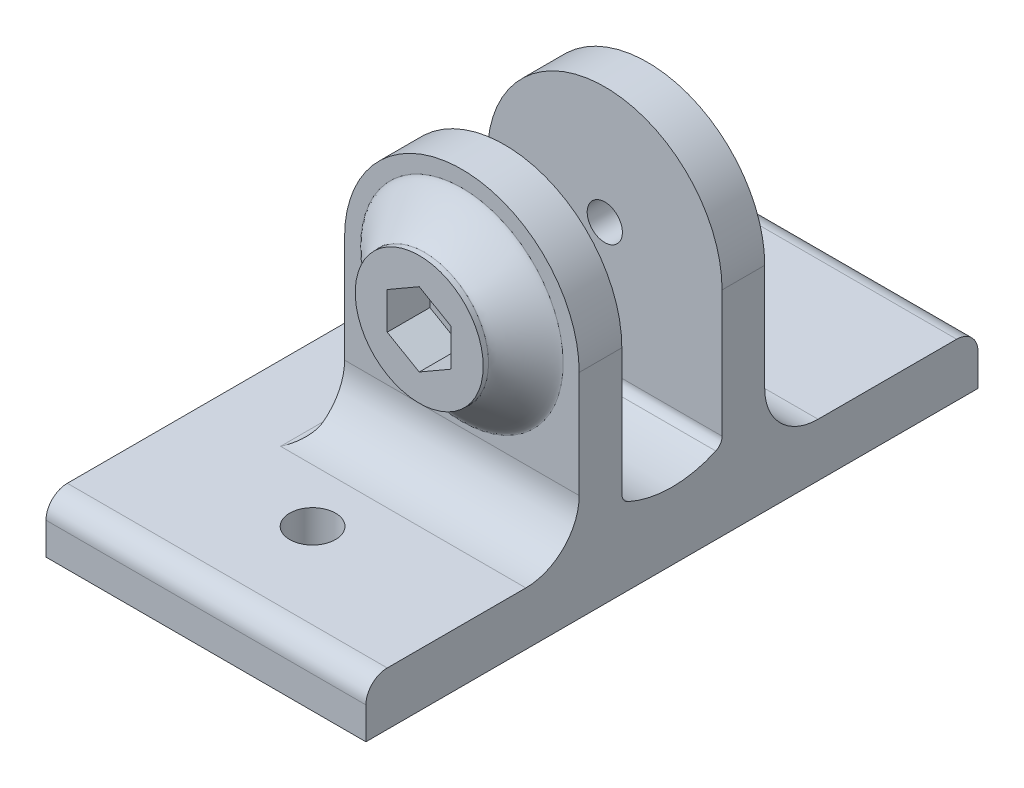
SolidWorks part; units mm, degrees
ref_plane "Front Plane" through (0, 0, 0) normal (0, 0, 1) x (1, 0, 0)
ref_plane "Top Plane" through (0, 0, 0) normal (0, 1, 0) x (1, 0, 0)
ref_plane "Right Plane" through (0, 0, 0) normal (1, 0, 0) x (0, 0, -1)
sketch "Croquis1" plane through (0, 0, 0) normal (0, 0, 1) x (1, 0, 0)
  line L0 (25.3159, 0) -> (-25.3159, 0) construction
  line L1 (11, 0) -> (11, -20)
  line L2 (11, -20) -> (-19, -20)
  line L3 (-11, 0) -> (-11, -15)
  line L6 (-11, -15) -> (-19, -15)
  line L7 (-19, -15) -> (-19, -20)
  arc A0 (11, 0) -> (-11, 0) centre (0, 0) ccw
  circle A1 centre (0, 0) radius 9 construction
  circle A5 centre (0, 0) radius 1.65
  point P7 (0, 0)
  dimension "D1" = 2
  dimension "D4" = 5
  dimension "D5" = 3.3
  dimension "D2" = 20
  dimension "D3" = 30
extrude "Saliente-Extruir1" add sketch "Croquis1" along normal blind 4 from offset 0.2
sketch "Croquis2" plane through (0, 0, 4.2) normal (0, 0, 1) x (1, 0, 0)
  line L1 (-19, -15) -> (11, -15)
  line L2 (-19, -15) -> (-19, -20)
  line L3 (-19, -20) -> (11, -20)
  line L4 (11, -15) -> (11, -20)
extrude "Saliente-Extruir2" add sketch "Croquis2" along normal blind 20
sketch "Croquis3" plane through (0, -15, 0) normal (0, 1, 0) x (1, 0, 0)
  line L1 (11, -14.2) -> (-19, -14.2) construction
  line L3 (11, -24.2) -> (11, -4.2) construction
  line L4 (-19, -24.2) -> (-19, -0.2) construction
  circle A0 centre (-4, -14.2) radius 2.15
  dimension "D1" = 4.3
  dimension "D2" = 15
extrude "Cortar-Extruir1" cut sketch "Croquis3" against normal through all
ref_plane "Plano1" through (0, 0, -4.5) normal (0, 0, -1) x (-1, 0, 0)
sketch "Croquis4" plane through (0, 0, 0.2) normal (0, 0, -1) x (-1, 0, 0)
  line L1 (19, -15) -> (-11, -15)
  line L2 (19, -15) -> (19, -20)
  line L3 (19, -20) -> (-11, -20)
  line L4 (-11, -15) -> (-11, -20)
extrude "Saliente-Extruir3" add sketch "Croquis4" along normal blind 10
mirror "Simetría1" about plane through (0, 0, -4.5) normal (0, 0, -1) of "Saliente-Extruir1", "Saliente-Extruir2", "Cortar-Extruir1"
sketch "Croquis5" plane through (0, 0, 4.2) normal (0, 0, 1) x (1, 0, 0)
  line L0 (-6, 0) -> (-6, -15)
  line L1 (3, 1.7321) -> (0, 3.4641)
  line L2 (0, 3.4641) -> (-3, 1.7321)
  line L3 (-3, 1.7321) -> (-3, -1.7321)
  line L4 (-3, -1.7321) -> (0, -3.4641)
  line L5 (0, -3.4641) -> (3, -1.7321)
  line L6 (3, -1.7321) -> (3, 1.7321)
  line L7 (11, -15) -> (-19, -15) construction
  line L8 (-6, -15) -> (6, -15)
  line L9 (6, -15) -> (6, 0)
  circle A0 centre (0, 0) radius 6
  circle A1 centre (0, 0) radius 3 construction
  circle A2 centre (0, 0) radius 1.65 construction
  circle A3 centre (0, 0) radius 1.65
  dimension "D1" = 6
  dimension "D2" = 12
extrude "Saliente-Extruir4" add sketch "Croquis5" along normal blind 4 contours A0 L6 L5 L4 L3 L2 L1 region at (0, 5.8303, 4.2)
chamfer "Chaflán2" distance 2.5 distance2 5 1 edges at (0, -15, 0.2) first distance on face at (1.65, 0, 0.2)
chamfer "Chaflán3" distance 5 distance2 2.5 1 edges at (0, -15, -9.2) first distance on face at (-4, -15, -25.35)
fillet "Redondeo1" radius 10 1 edges at (0, -14.85, -4.5)
fillet "Redondeo2" radius 1 1 edges at (0, -12.5, -9.2)
fillet "Redondeo3" radius 1 1 edges at (0, -12.5, 0.2)
sketch "Croquis6" plane through (0, -15, 0) normal (0, 1, 0) x (1, 0, 0)
  circle A0 centre (-4, -14.2) radius 3.5 construction
  dimension "D1" = 7
fillet "Redondeo4" radius 5 1 edges at (0, -15, 4.2)
fillet "Redondeo5" radius 5 1 edges at (0, -15, -13.2)
fillet "Redondeo6" radius 2 2 edges at (-4, -15, -33.2) (-4, -15, 24.2)
fillet "Redondeo7" radius 1 2 edges at (-11, -15, 2.5) (-11, -15, -11.2)
fillet "Redondeo8" radius 3.5 1 edges at (6, 0, 4.2) conic rho 0.1
